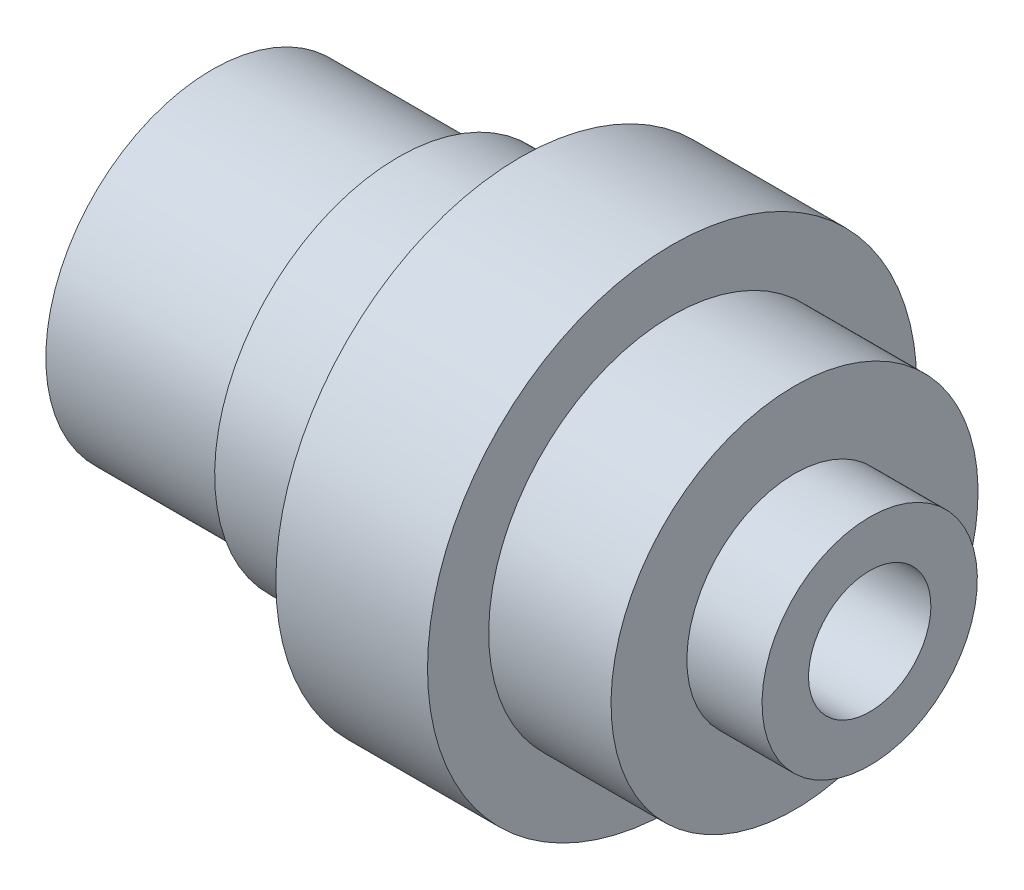
SolidWorks part; units mm, degrees
ref_plane "Front Plane" through (0, 0, 0) normal (0, 0, 1) x (1, 0, 0)
ref_plane "Top Plane" through (0, 0, 0) normal (0, 1, 0) x (1, 0, 0)
ref_plane "Right Plane" through (0, 0, 0) normal (1, 0, 0) x (0, 0, -1)
sketch "Sketch1" plane through (0, 0, 0) normal (0, 0, 1) x (1, 0, 0)
  line L0 (0, 0) -> (0, 8.636)
  line L1 (0, 8.636) -> (9.652, 8.636)
  line L2 (9.652, 8.636) -> (9.652, 9.525)
  line L3 (9.652, 9.525) -> (16.002, 9.525)
  line L4 (16.002, 9.525) -> (16.002, 12.7)
  line L5 (16.002, 12.7) -> (23.876, 12.7)
  line L6 (23.876, 12.7) -> (23.876, 9.525)
  line L7 (23.876, 9.525) -> (30.226, 9.525)
  line L8 (30.226, 9.525) -> (30.226, 5.588)
  line L9 (30.226, 5.588) -> (34.1274, 5.588)
  line L10 (34.1274, 5.588) -> (34.1274, 0)
  line L11 (34.1274, 0) -> (0, 0)
  line L12 (34.1274, 3.175) -> (0, 3.175)
  line L13 (34.1274, 0) -> (34.1274, 3.175)
  dimension "D1" = 9.652
  dimension "D2" = 6.35
  dimension "D3" = 7.874
  dimension "D4" = 6.35
  dimension "D5" = 3.9014
  dimension "D6" = 3.937
  dimension "D7" = 3.175
  dimension "D8" = 3.175
  dimension "D9" = 0.889
  dimension "D10" = 8.636
  dimension "D11" = 3.175
revolve "Revolve1" add sketch "Sketch1" angle 360 about L11 region at (16.81, 6.7041, 0)
